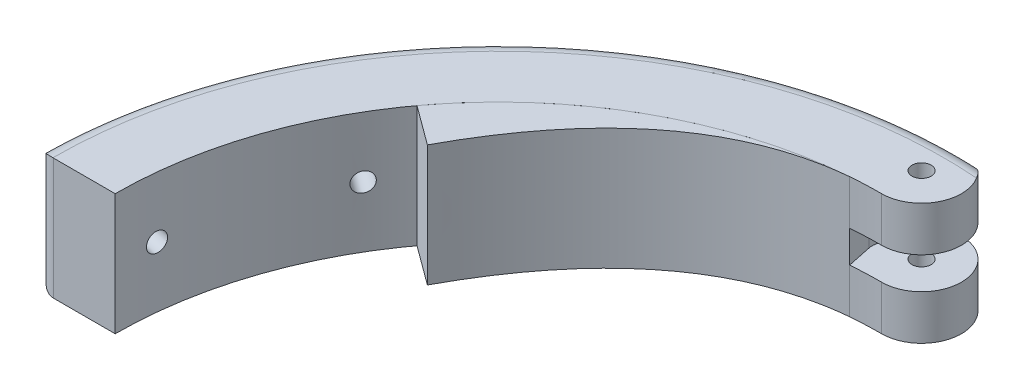
SolidWorks part; units mm, degrees
ref_plane "Front Plane" through (0, 0, 0) normal (0, 0, 1) x (1, 0, 0)
ref_plane "Top Plane" through (0, 0, 0) normal (0, 1, 0) x (1, 0, 0)
ref_plane "Right Plane" through (0, 0, 0) normal (1, 0, 0) x (0, 0, -1)
sketch "Sketch1" plane through (0, 0, 0) normal (0, 1, 0) x (1, 0, 0)
  line L0 (-0.2546, -0.0735) -> (24.7454, -0.0735)
  line L2 (144.7454, 119.9265) -> (144.7454, 144.9265)
  line L3 (-0.2546, -0.0735) -> (301.2049, -0.0735) construction
  line L4 (144.7454, -153.9705) -> (144.7454, 153.8235) construction
  arc A0 (24.7454, -0.0735) -> (144.7454, 119.9265) centre (144.7454, -0.0735) cw
  arc A1 (-0.2546, -0.0735) -> (144.7454, 144.9265) centre (144.7454, -0.0735) cw
  point P7 (144.7454, -0.0735)
  point P11 (144.7454, -0.0735)
  dimension "D1" = 25
extrude "Boss-Extrude1" add sketch "Sketch1" along normal blind 38
extrude "Cut-Extrude1" cut sketch "Sketch2" against normal through all
sketch "Sketch2" plane through (187.0795, -46.1724, -236.427) normal (0.8056, 0, 0.5924) x (0.5924, 0.0036, -0.8056)
  circle A0 centre (-227.475, 65.9963) radius 3
extrude "Cut-Extrude2" cut sketch "Sketch3" against normal through all
sketch "Sketch3" plane through (59.9415, -46.1724, -112.2008) normal (0.9788, 0, 0.2048) x (0.2045, 0.0528, -0.9774)
  circle A0 centre (-101.2299, 70.6123) radius 3
sketch "Sketch4" plane through (0, 38, 0) normal (0, 1, 0) x (1, 0, 0)
  line L0 (144.7454, 119.9265) -> (144.7454, 144.9265) construction
  line L1 (144.7454, 144.9265) -> (144.7454, -18.1646) construction
  line L2 (0, 0) -> (179.8224, 0) construction
  line L4 (144.7454, 141.9265) -> (144.7454, 144.9265)
  line L5 (135.2454, 132.4265) -> (132.5495, 131.7962)
  line L6 (132.5495, 131.7962) -> (135.1075, 119.5386)
  arc A0 (144.7454, 119.9265) -> (144.7454, 144.9265) centre (144.7454, 132.4265) ccw
  circle A2 centre (144.7454, 132.4265) radius 3
  arc A3 (144.7454, 119.9265) -> (135.1075, 119.5386) centre (144.7454, 0) ccw
  arc A4 (144.7454, 144.9265) -> (144.7454, 119.9265) centre (144.7454, 132.4265) ccw construction
  arc A6 (144.7454, 141.9265) -> (135.2454, 132.4265) centre (144.7454, 132.4265) ccw
  point P16 (132.5495, 131.7962)
  dimension "D1" = 9.5
  dimension "D2" = 6
extrude "Boss-Extrude2" add sketch "Sketch4" against normal up to surface (38 mm away) up to face at (64.7746, 0, -79.8973)
extrude "Cut-Extrude3" cut sketch "Sketch4<2>" against normal blind 24
sketch "Sketch4<2>" plane through (0, 38, 0) normal (0, 1, 0) x (1, 0, 0) same geometry as "Sketch4"
extrude "Boss-Extrude3" add sketch "Sketch4<3>" against normal blind 14
sketch "Sketch4<3>" plane through (0, 38, 0) normal (0, 1, 0) x (1, 0, 0) same geometry as "Sketch4"
extrude "Cut-Extrude4" cut sketch "Sketch4<4>" against normal through all contours A2
sketch "Sketch4<4>" plane through (0, 38, 0) normal (0, 1, 0) x (1, 0, 0) same geometry as "Sketch4"
sketch "Sketch5" plane through (0, 0, 0) normal (0, -1, 0) x (1, 0, 0)
  line L1 (151.6736, -132.4265) -> (148.2095, -126.4265)
  line L2 (148.2095, -126.4265) -> (141.2813, -126.4265)
  line L3 (141.2813, -126.4265) -> (137.8172, -132.4265)
  line L4 (137.8172, -132.4265) -> (141.2813, -138.4265)
  line L5 (141.2813, -138.4265) -> (148.2095, -138.4265)
  line L6 (148.2095, -138.4265) -> (151.6736, -132.4265)
  circle A0 centre (144.7454, -132.4265) radius 6 construction
  dimension "D1" = 12
extrude "Cut-Extrude5" cut sketch "Sketch5" against normal blind 6
fillet "Fillet1" radius 5.5 2 edges at (42.2149, 0, -102.457) (42.2149, 38, -102.457) tangent propagation no
fillet "Fillet2" radius 5.5 2 edges at (144.7454, 19, -141.9265) (132.5495, 19, -131.7962)
fillet "Fillet3" radius 5.5 1 edges at (-0.2546, 19, 0.0735) tangent propagation no
sketch "Sketch7" plane through (0, 38, 0) normal (0, 1, 0) x (1, 0, 0)
  line L0 (5.3539, -0.0735) -> (24.7454, -0.0735) construction
  line L1 (24.7454, -0.0735) -> (236.7545, -0.0735) construction
  line L2 (60.3901, 62.0394) -> (48.1093, 71.0705)
  arc A0 (135.1074, 119.5388) -> (24.7454, -0.0735) centre (144.7454, -0.0735) ccw construction
  arc A1 (48.1093, 71.0705) -> (135.1074, 119.5388) centre (144.7454, -0.0735) cw
  spline S0 degree 2 poles (60.3901, 62.0394) (88.9095, 115.1517) (135.1074, 119.5388) knots 0 0 0 0.907186 0.907186 0.907186
  dimension "D1" = 36.33
extrude "Boss-Extrude4" add sketch "Sketch7" against normal up to surface (38 mm away) separate body up to face at (144.7454, 0, -132.4265)
